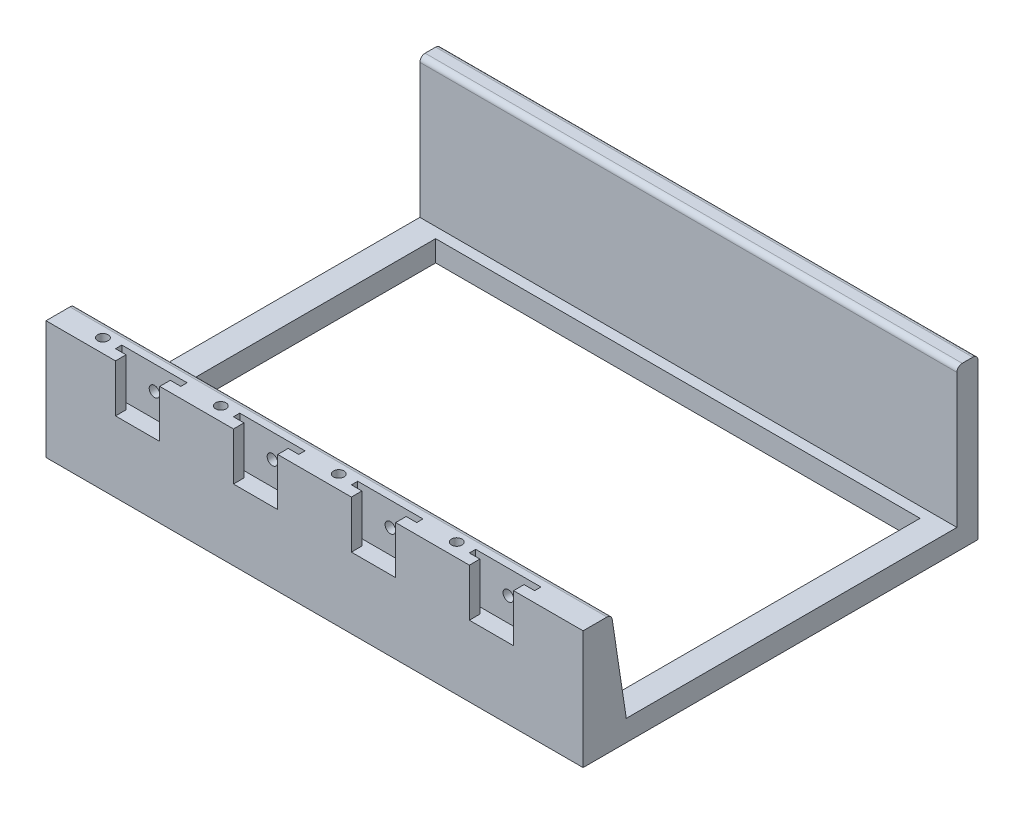
SolidWorks part; units mm, degrees
ref_plane "前视基准面" through (0, 0, 0) normal (0, 0, 1) x (1, 0, 0)
ref_plane "上视基准面" through (0, 0, 0) normal (0, 1, 0) x (1, 0, 0)
ref_plane "右视基准面" through (0, 0, 0) normal (1, 0, 0) x (0, 0, -1)
other "Configuration Table"
sketch "草图1" plane through (0, 0, 0) normal (0, 1, 0) x (1, 0, 0)
  line L1 (0, 0) -> (-102, 0)
  line L2 (0, 0) -> (0, 75)
  line L3 (0, 75) -> (-102, 75)
  line L4 (-102, 0) -> (-102, 75)
  dimension "D1" = 102
  dimension "D2" = 75
extrude "凸台-拉伸1" add sketch "草图1" along normal blind 22.5
sketch "草图2" plane through (0, 22.5, 0) normal (0, 1, 0) x (1, 0, 0)
  line L0 (-102, 75) -> (-102, 0) construction
  line L1 (-90.8, 2) -> (-88.8, 2)
  line L2 (-90.8, 2) -> (-90.8, 3.2)
  line L3 (-90.8, 3.2) -> (-78.4, 3.2)
  line L4 (-78.4, 2) -> (-78.4, 3.2)
  line L5 (-68.4, 2) -> (-66.4, 2)
  line L6 (-68.4, 2) -> (-68.4, 3.2)
  line L7 (-68.4, 3.2) -> (-56, 3.2)
  line L8 (-56, 2) -> (-56, 3.2)
  line L9 (-46, 3.2) -> (-33.6, 3.2)
  line L10 (-46, 3.2) -> (-46, 2)
  line L11 (-46, 2) -> (-44, 2)
  line L12 (-33.6, 3.2) -> (-33.6, 2)
  line L13 (-23.6, 3.2) -> (-11.2, 3.2)
  line L14 (-23.6, 3.2) -> (-23.6, 2)
  line L15 (-23.6, 2) -> (-21.6, 2)
  line L16 (-11.2, 3.2) -> (-11.2, 2)
  line L19 (-102, 0) -> (0, 0) construction
  line L20 (-13.2, 2) -> (-11.2, 2)
  line L22 (-88.8, 2) -> (-88.8, 0)
  line L23 (-88.8, 0) -> (-80.4, 0)
  line L24 (-80.4, 2) -> (-80.4, 0)
  line L26 (-66.4, 2) -> (-66.4, 0)
  line L27 (-66.4, 0) -> (-58, 0)
  line L28 (-58, 2) -> (-58, 0)
  line L30 (-44, 2) -> (-44, 0)
  line L31 (-44, 0) -> (-35.6, 0)
  line L32 (-35.6, 2) -> (-35.6, 0)
  line L34 (-21.6, 2) -> (-21.6, 0)
  line L35 (-21.6, 0) -> (-13.2, 0)
  line L36 (-13.2, 2) -> (-13.2, 0)
  line L37 (-35.6, 2) -> (-33.6, 2)
  line L38 (-58, 2) -> (-56, 2)
  line L39 (-80.4, 2) -> (-78.4, 2)
  point P16 (-68.4, 2.6)
  dimension "D1" = 12.4
  dimension "D2" = 12.4
  dimension "D3" = 12.4
  dimension "D4" = 12.4
  dimension "D5" = 10
  dimension "D6" = 10
  dimension "D7" = 10
  dimension "D8" = 11.2
  dimension "D9" = 2
  dimension "D10" = 2
  dimension "D11" = 2
  dimension "D12" = 2
  dimension "D13" = 1.2
  dimension "D14" = 1.2
  dimension "D15" = 1.2
  dimension "D16" = 1.2
  dimension "D17" = 2
  dimension "D18" = 2
  dimension "D19" = 2
  dimension "D20" = 2
  dimension "D21" = 2
  dimension "D22" = 2
  dimension "D23" = 2
  dimension "D24" = 2
extrude "切除-拉伸1" cut sketch "草图2" against normal offset from surface (9.06 mm away) 13.44 up to face at (-51, 0, -37.5)
sketch "草图3" plane through (0, 22.5, 0) normal (0, 1, 0) x (1, 0, 0)
  line L0 (0, 0) -> (0, 75) construction
  line L1 (-102, 75) -> (0, 75)
  line L2 (-102, 75) -> (-102, 8.2)
  line L3 (-102, 8.2) -> (0, 8.2)
  line L4 (0, 75) -> (0, 8.2)
  line L5 (-11.2, 3.2) -> (-23.6, 3.2) construction
  dimension "D1" = 5
extrude "切除-拉伸2" cut sketch "草图3" against normal blind 12
sketch "草图4" plane through (-102, 0, 0) normal (-1, 0, 0) x (0, 0, 1)
  line L6 (-75, 10.5) -> (-8.2, 10.5) construction
  line L7 (-71, 10.5) -> (-8.2, 10.5)
  line L8 (-71, 10.5) -> (-71, 4)
  line L9 (-71, 4) -> (-8.2, 4)
  line L10 (-8.2, 10.5) -> (-8.2, 4)
  line L11 (-75, 10.5) -> (-75, 0) construction
  line L12 (-75, 0) -> (0, 0) construction
  line L13 (-8.2, 10.5) -> (-8.2, 22.5) construction
  dimension "D1" = 4
  dimension "D2" = 4
extrude "切除-拉伸3" cut sketch "草图4" against normal through all
sketch "草图6" plane through (0, 10.5, 0) normal (0, 1, 0) x (1, 0, 0)
  line L4 (-102, 71) -> (0, 71)
  line L5 (0, 71) -> (0, 75)
  line L6 (0, 75) -> (-102, 75)
  line L7 (-102, 75) -> (-102, 71)
  line L8 (-102, 71) -> (0, 71)
  line L9 (0, 71) -> (0, 75)
  line L10 (0, 75) -> (-102, 75)
  line L11 (-102, 75) -> (-102, 71)
  dimension "D1" = 0
extrude "凸台-拉伸2" add sketch "草图6" along normal blind 20
sketch "草图7" plane through (0, 4, 0) normal (0, 1, 0) x (1, 0, 0)
  line L0 (0, 71) -> (0, 8.2) construction
  line L1 (-97, 69) -> (-5, 69)
  line L2 (-97, 69) -> (-97, 10.2)
  line L3 (-97, 10.2) -> (-5, 10.2)
  line L4 (-5, 69) -> (-5, 10.2)
  line L5 (-102, 71) -> (-102, 8.2) construction
  line L6 (-102, 71) -> (0, 71) construction
  line L7 (0, 8.2) -> (-102, 8.2) construction
  dimension "D1" = 5
  dimension "D2" = 5
  dimension "D3" = 2
  dimension "D4" = 2
extrude "切除-拉伸5" cut sketch "草图7" against normal blind 8
sketch "草图9" plane through (-102, 0, 0) normal (-1, 0, 0) x (0, 0, 1)
  line L0 (-8.2, 22.5) -> (-5.4, 22.5)
  line L2 (-5.4, 22.5) -> (-8.2, 4)
  line L3 (-8.2, 4) -> (-8.2, 22.5)
  dimension "D1" = 2.8
extrude "切除-拉伸6" cut sketch "草图9" against normal blind 108
fillet "圆角2" radius 1 3 edges at (-51, 30.5, -75) (-51, 30.5, -71) (-51, 22.5, -5.4)
sketch "草图10" plane through (0, 0, -3.2) normal (0, 0, 1) x (1, 0, 0)
  line L0 (-88.8, 22.5) -> (-80.4, 13.44) construction
  line L1 (-80.4, 22.5) -> (-88.8, 13.44) construction
  line L2 (-66.4, 22.5) -> (-58, 13.44) construction
  line L3 (-51, 0) -> (-51, 38.7871) construction
  line L4 (-58, 22.5) -> (-66.4, 13.44) construction
  line L5 (-102, 0) -> (0, 0) construction
  circle A0 centre (-84.6, 17.97) radius 1
  circle A1 centre (-62.2, 17.97) radius 1
  circle A2 centre (-39.8, 17.97) radius 1
  circle A3 centre (-17.4, 17.97) radius 1
  dimension "D1" = 2
  dimension "D2" = 2
extrude "切除-拉伸7" cut sketch "草图10" against normal blind 10
sketch "草图14" plane through (0, 22.5, 0) normal (0, 1, 0) x (1, 0, 0)
  line L0 (-23.6, 2) -> (-21.6, 2) construction
  line L1 (-23.6, 2) -> (-23.6, 3.2) construction
  line L2 (-46, 2) -> (-46, 3.2) construction
  line L3 (-68.4, 3.2) -> (-68.4, 2) construction
  line L4 (-90.8, 3.2) -> (-90.8, 2) construction
  circle A0 centre (-93.8, 2.6) radius 1
  circle A1 centre (-71.4, 2.6) radius 1
  circle A2 centre (-49, 2.6) radius 1
  circle A3 centre (-26.6, 2.6) radius 1
  dimension "D1" = 2
  dimension "D2" = 0.6
  dimension "D3" = 3
  dimension "D4" = 3
  dimension "D5" = 2
  dimension "D6" = 3
  dimension "D7" = 2
  dimension "D8" = 3
  dimension "D9" = 2
extrude "切除-拉伸8" cut sketch "草图14" against normal blind 10
